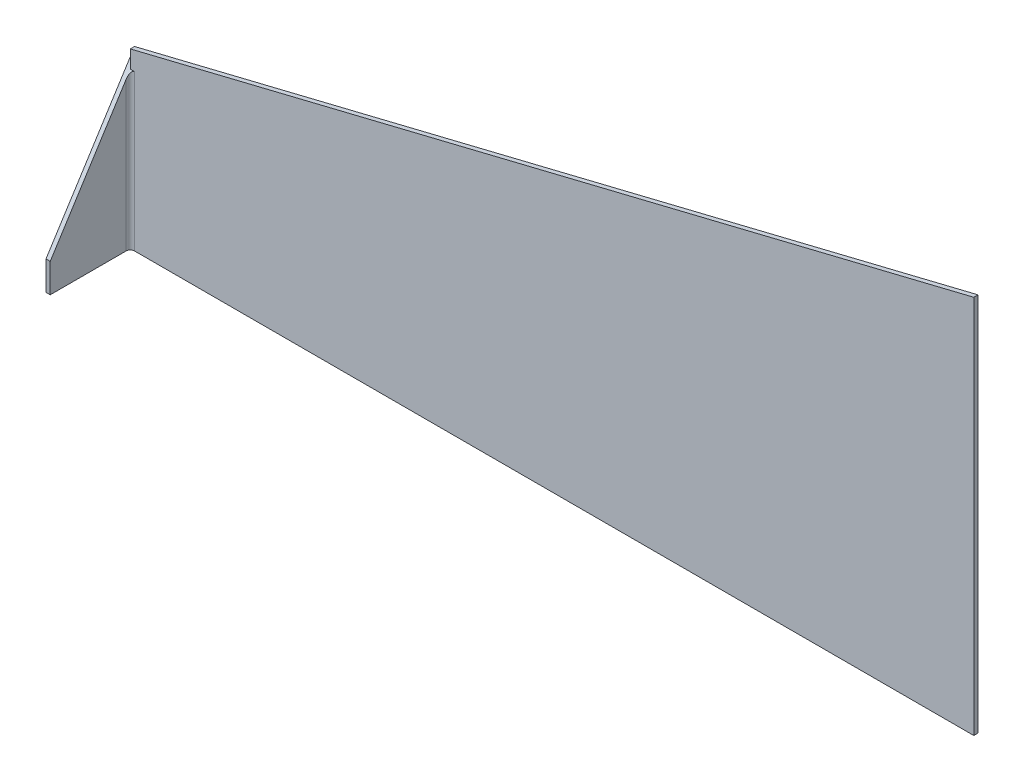
SolidWorks part; units mm, degrees
ref_plane "Front Plane" through (0, 0, 0) normal (0, 0, 1) x (1, 0, 0)
ref_plane "Top Plane" through (0, 0, 0) normal (0, 1, 0) x (1, 0, 0)
ref_plane "Right Plane" through (0, 0, 0) normal (1, 0, 0) x (0, 0, -1)
sketch "Sketch1" plane through (0, 0, 0) normal (0, 0, 1) x (1, 0, 0)
  line L0 (0, 0) -> (-200, 0)
  line L1 (-200, 0) -> (-200, 41)
  line L2 (-200, 41) -> (0, 90)
  line L3 (0, 90) -> (0, 0)
  dimension "D1" = 200
  dimension "D2" = 41
  dimension "D3" = 90
extrude "Boss-Extrude1" add sketch "Sketch1" along normal blind 1 contours L2 L3 L0 L1
sketch "Sketch2" plane through (-200, 0, 0) normal (-1, 0, 0) x (0, 0, 1)
  line L0 (0, 38.4183) -> (20, 6.8754)
  line L1 (0, 0) -> (0, 41) construction
  line L2 (20, 6.8754) -> (20, 0)
  line L3 (20, 0) -> (0, 0)
  line L4 (0, 0) -> (0, 38.4183)
  point P4 (0, 38.4183)
  point P8 (20, 6.8754)
  dimension "D1" = 20
extrude "Boss-Extrude2" add sketch "Sketch2" along normal blind 1
fillet "Fillet1" radius 1 1 edges at (-200, 18.4206, 1)
